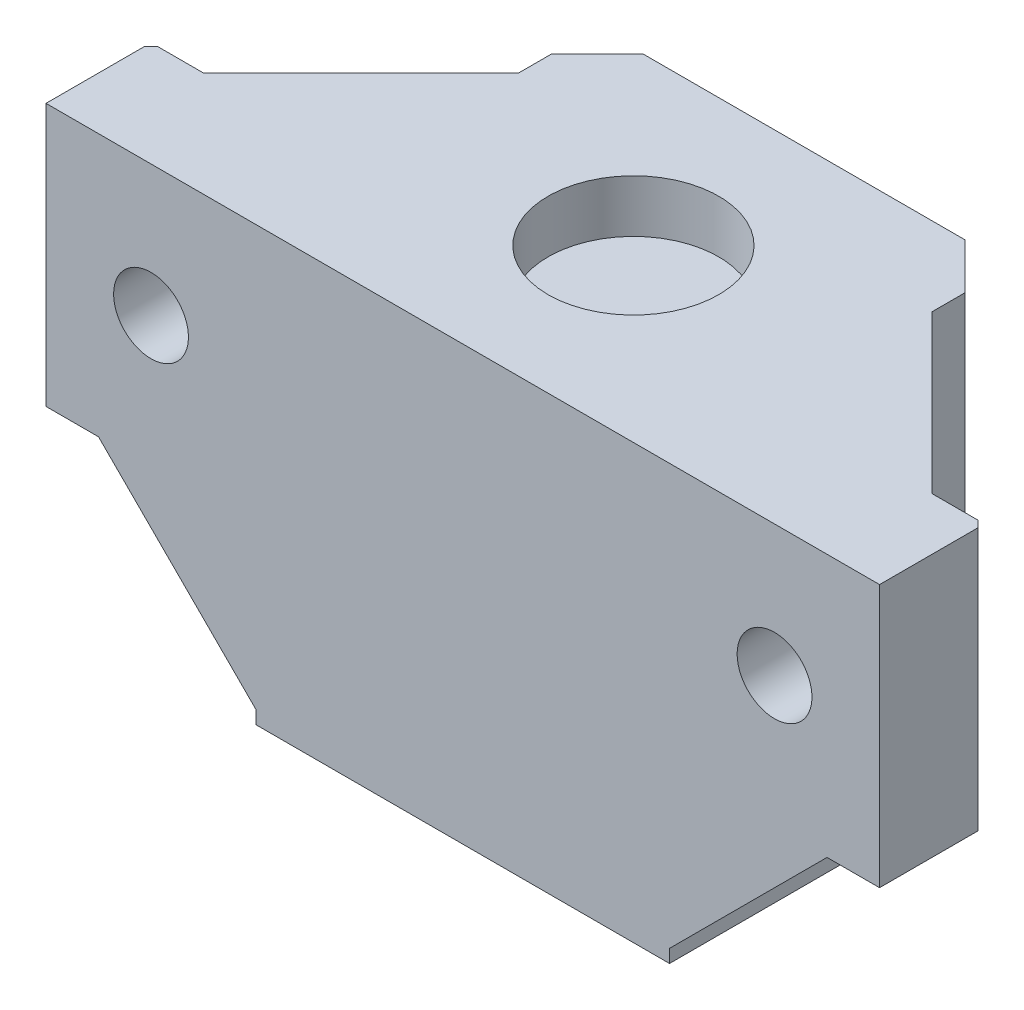
SolidWorks part; units mm, degrees
ref_plane "Front Plane" through (0, 0, 0) normal (0, 0, 1) x (1, 0, 0)
ref_plane "Top Plane" through (0, 0, 0) normal (0, 1, 0) x (1, 0, 0)
ref_plane "Right Plane" through (0, 0, 0) normal (1, 0, 0) x (0, 0, -1)
sketch "Sketch1" plane through (0, 0, 0) normal (0, 1, 0) x (1, 0, 0)
  line L1 (-15.75, 8.1101) -> (15.75, 8.1101)
  line L2 (-15.75, 8.1101) -> (-15.75, -17.8899)
  line L4 (15.75, 8.1101) -> (15.75, -17.8899)
  line L7 (-15.75, -17.8899) -> (15.75, -17.8899)
  point P4 (0, 8.1101)
  dimension "D1" = 31.5
  dimension "D3" = 26
extrude "Boss-Extrude1" add sketch "Sketch1" along normal blind 33
sketch "Sketch8" plane through (0, 0, 17.8899) normal (0, 0, 1) x (1, 0, 0)
  line L1 (15.75, 33) -> (31.75, 33)
  line L2 (15.75, 33) -> (15.75, 13)
  line L3 (15.75, 13) -> (31.75, 13)
  line L4 (31.75, 33) -> (31.75, 13)
  line L5 (-15.75, 33) -> (-31.75, 33)
  line L6 (-15.75, 33) -> (-15.75, 13)
  line L7 (-15.75, 13) -> (-31.75, 13)
  line L8 (-31.75, 33) -> (-31.75, 13)
  dimension "D1" = 16
  dimension "D2" = 16
  dimension "D3" = 20
extrude "Boss-Extrude2" add sketch "Sketch8" against normal blind 8
sketch "Sketch2" plane through (0, 33, 0) normal (0, -1, 0) x (1, 0, 0)
  line L1 (-11.25, 14.3899) -> (-5.5, 14.3899)
  line L2 (-11.25, 14.3899) -> (-11.25, -4.6101)
  line L3 (-11.25, -4.6101) -> (-5.5, -4.6101)
  line L4 (11.25, 14.3899) -> (11.25, -4.6101)
  line L5 (15.75, -8.1101) -> (-15.75, -8.1101) construction
  line L7 (-5.5, -4.6101) -> (-5.5, -1.6101)
  line L8 (-5.5, -1.6101) -> (5.5, -1.6101)
  line L9 (5.5, -4.6101) -> (5.5, -1.6101)
  line L10 (-15.75, -8.1101) -> (-15.75, 17.8899) construction
  line L11 (15.75, 17.8899) -> (15.75, -8.1101) construction
  line L12 (5.5, -4.6101) -> (11.25, -4.6101)
  line L13 (-15.75, 17.8899) -> (15.75, 17.8899) construction
  line L14 (5.5, 14.3899) -> (11.25, 14.3899)
  line L16 (-5.5, 14.3899) -> (-5.5, 11.3899)
  line L17 (-5.5, 11.3899) -> (5.5, 11.3899)
  line L18 (5.5, 14.3899) -> (5.5, 11.3899)
  point P16 (0, -1.6101)
  dimension "D1" = 3.5
  dimension "D2" = 4.5
  dimension "D3" = 4.5
  dimension "D4" = 3
  dimension "D5" = 11
  dimension "D6" = 3.5
extrude "Cut-Extrude1" cut sketch "Sketch2" along normal through all from offset 10
sketch "Sketch3" plane through (0, 0, 9.8899) normal (0, 0, -1) x (-1, 0, 0)
  line L2 (-31.75, 13) -> (-31.75, 33) construction
  line L3 (31.75, 33) -> (31.75, 13) construction
  line L4 (-31.75, 33) -> (-15.75, 33) construction
  circle A0 centre (-23.75, 23) radius 2.85
  circle A1 centre (23.75, 23) radius 2.85
  dimension "D1" = 5.7
  dimension "D2" = 8
  dimension "D3" = 10
  dimension "D4" = 8
extrude "Cut-Extrude2" cut sketch "Sketch3" against normal through all
sketch "Sketch6" plane through (0, 0, 9.8899) normal (0, 0, -1) x (-1, 0, 0)
  circle A0 centre (-23.75, 23) radius 6.25
  circle A1 centre (23.75, 23) radius 6.25
  dimension "D1" = 12.5
extrude "Cut-Extrude5" cut sketch "Sketch6" against normal blind 2
sketch "Sketch4" plane through (0, 33, 0) normal (0, 1, 0) x (1, 0, 0)
  line L0 (-31.75, -17.8899) -> (31.75, -17.8899) construction
  circle A0 centre (0, -4.8899) radius 2.35
  dimension "D1" = 4.7
  dimension "D2" = 13
extrude "Cut-Extrude3" cut sketch "Sketch4" against normal through all
sketch "Sketch5" plane through (0, 33, 0) normal (0, 1, 0) x (1, 0, 0)
  circle A0 centre (0, -4.8899) radius 6.5
  dimension "D1" = 13
extrude "Cut-Extrude4" cut sketch "Sketch5" against normal blind 4
chamfer "Chamfer1" distance 3.5 angle 45 2 edges at (-15.75, 16.5, -8.1101) (15.75, 16.5, -8.1101)
chamfer "Chamfer3" distance 0.5 angle 45 2 edges at (31.75, 23, 9.8899) (-31.75, 23, 9.8899)
chamfer "Chamfer4" distance 12 angle 45 2 edges at (15.75, 23, 9.8899) (-15.75, 23, 9.8899)
chamfer "Chamfer5" distance 12 angle 45 2 edges at (-15.75, 13, 7.8899) (15.75, 13, 7.8899)
sketch "Sketch10" plane through (0, 29, 0) normal (0, 1, 0) x (1, 0, 0)
  circle A0 centre (0, -4.8899) radius 4.4281
  point P3 (-20.6242, -24.6998)
extrude "Boss-Extrude4" add sketch "Sketch10" against normal blind 0.65
sketch "Sketch11" plane through (0, 0, 11.8899) normal (0, 0, -1) x (-1, 0, 0)
  circle A0 centre (-23.75, 23) radius 4.527
  circle A1 centre (23.75, 23) radius 4.4505
extrude "Boss-Extrude5" add sketch "Sketch11" against normal blind 0.65
